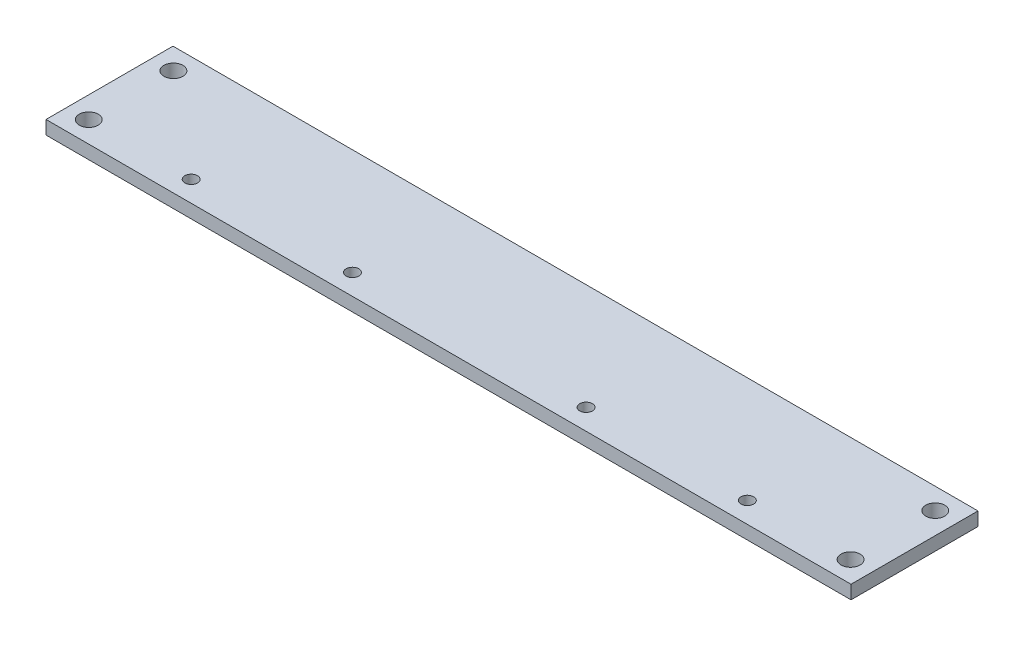
SolidWorks part; units mm, degrees
ref_plane "Front Plane" through (0, 0, 0) normal (0, 0, 1) x (1, 0, 0)
ref_plane "Top Plane" through (0, 0, 0) normal (0, 1, 0) x (1, 0, 0)
ref_plane "Right Plane" through (0, 0, 0) normal (1, 0, 0) x (0, 0, -1)
sketch "Sketch1" plane through (0, 0, 0) normal (0, 1, 0) x (1, 0, 0)
  line L1 (-95.1, -15) -> (95.1, -15)
  line L2 (-95.1, -15) -> (-95.1, 15)
  line L3 (-95.1, 15) -> (95.1, 15)
  line L4 (95.1, -15) -> (95.1, 15)
  line L5 (-95.1, -15) -> (95.1, 15) construction
  line L6 (-95.1, 15) -> (95.1, -15) construction
  point P0 (0, 0)
  dimension "D1" = 190.2
  dimension "D2" = 30
extrude "Boss-Extrude1" add sketch "Sketch1" along normal blind 3.2
sketch "Sketch2" plane through (0, 3.2, 0) normal (0, 1, 0) x (1, 0, 0)
  line L1 (-90, -10) -> (90, -10) construction
  line L2 (-90, -10) -> (-90, 10) construction
  line L3 (-90, 10) -> (90, 10) construction
  line L4 (90, -10) -> (90, 10) construction
  line L5 (-90, -10) -> (90, 10) construction
  line L6 (-90, 10) -> (90, -10) construction
  circle A0 centre (-90, 10) radius 2.25
  circle A1 centre (-90, -10) radius 2.25
  circle A2 centre (90, 10) radius 2.25
  circle A3 centre (90, -10) radius 2.25
  point P0 (0, 0)
  dimension "D3" = 4.5
  dimension "D1" = 20
  dimension "D2" = 180
extrude "Cut-Extrude1" cut sketch "Sketch2" against normal through all
sketch "Sketch3" plane through (0, 3.2, 0) normal (0, 1, 0) x (1, 0, 0)
  line L0 (-95.1, -10.1) -> (95.1, -10.1) construction
  line L1 (-95.1, 15) -> (-95.1, -15) construction
  line L2 (95.1, -15) -> (95.1, 15) construction
  circle A0 centre (65.7, -10.1) radius 1.5
  circle A1 centre (27.6, -10.1) radius 1.5
  circle A2 centre (-27.6, -10.1) radius 1.5
  circle A3 centre (-65.7, -10.1) radius 1.5
  circle A4 centre (90, -10) radius 2.25 construction
  circle A5 centre (-90, -10) radius 2.25 construction
  dimension "D1" = 3
  dimension "D2" = 24.3
  dimension "D3" = 24.3
  dimension "D4" = 0.1
  dimension "D5" = 38.1
  dimension "D6" = 38.1
extrude "Cut-Extrude2" cut sketch "Sketch3" against normal through all
